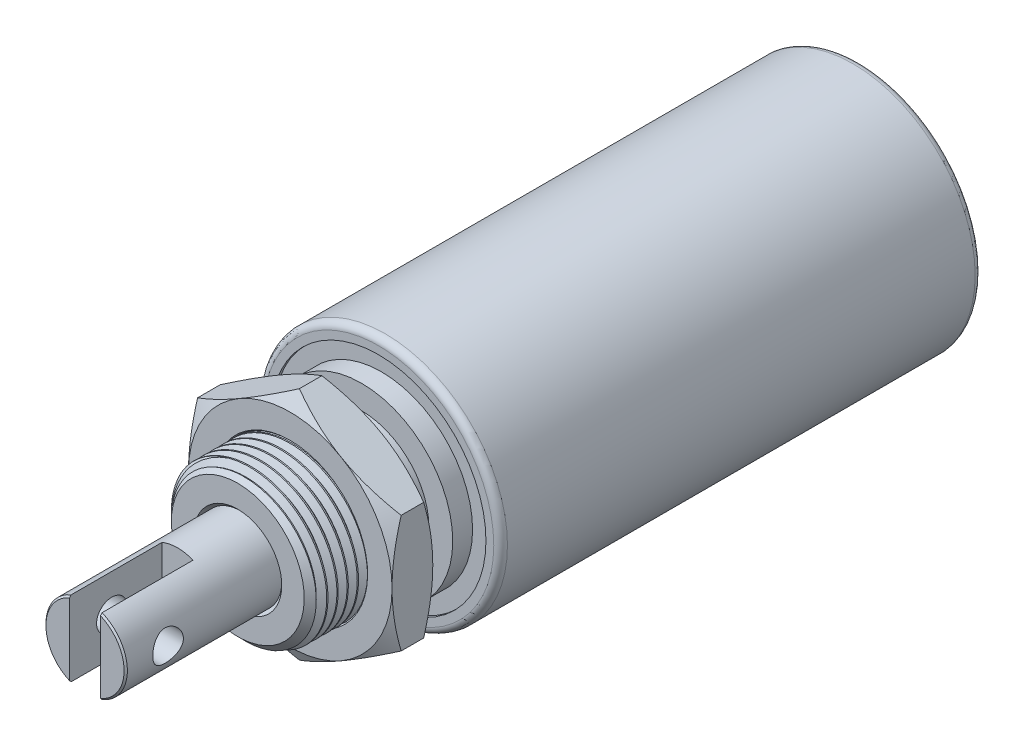
SolidWorks part; units mm, degrees
ref_plane "Front Plane" through (0, 0, 0) normal (0, 0, 1) x (1, 0, 0)
ref_plane "Top Plane" through (0, 0, 0) normal (0, 1, 0) x (1, 0, 0)
ref_plane "Right Plane" through (0, 0, 0) normal (1, 0, 0) x (0, 0, -1)
sketch "Sketch0" plane through (0, 0, 0) normal (1, 0, 0) x (0, 0, -1)
  line L0 (0, 0) -> (39.083, 0) construction
  line L1 (0, 0) -> (-21.5646, 0) construction
  line L2 (39.083, 9.525) -> (39.083, -9.525) construction
  line L3 (0, 5.9436) -> (0, -5.9436) construction
  line L4 (-21.5646, 3.175) -> (-21.5646, -3.175) construction
  line L5 (-21.5646, 0) -> (-34.2646, 0) construction
  point P10 (-18.2626, 0)
  point P12 (-9.652, 0)
  dimension "D1" = 18.2626
  dimension "Lg." = 39.083
  dimension "Dia." = 19.05
  dimension "Rod Dia." = 6.35
  dimension "A" = 21.5646
  dimension "Thread OD" = 11.8872
  dimension "Stroke" = 12.7
  dimension "D2" = 3.302
  dimension "D3" = 9.652
sketch "Sketch1" plane through (0, 0, 0) normal (1, 0, 0) x (0, 0, -1)
  line L0 (39.083, 0) -> (0, 0) construction
  line L1 (38.3286, 9.525) -> (1.8542, 9.525)
  line L2 (39.083, 2.0066) -> (39.083, 0)
  line L3 (39.083, 0) -> (0, 0)
  line L4 (1.5494, 8.382) -> (1.5494, 7.112)
  line L5 (38.862, 2.2276) -> (38.862, 8.9916)
  line L6 (1.3208, 8.9916) -> (1.3208, 8.382)
  line L7 (1.3208, 8.382) -> (1.5494, 8.382)
  line L8 (1.5494, 7.112) -> (0, 7.112)
  line L9 (0, 7.112) -> (0, 0)
  arc A0 (39.083, 2.0066) -> (38.862, 2.2276) centre (38.862, 2.0066) ccw
  arc A1 (38.862, 8.9916) -> (38.3286, 9.525) centre (38.3286, 8.9916) ccw
  arc A2 (1.3208, 8.9916) -> (1.8542, 9.525) centre (1.8542, 8.9916) cw
  dimension "D1" = 0.5334
  dimension "D4" = 1.3208
  dimension "D2" = 0.221
  dimension "D3" = 4.0132
  dimension "D5" = 16.764
  dimension "D6" = 0.2286
  dimension "D7" = 14.224
revolve "Revolve1" add sketch "Sketch1" angle 360 mid plane about L0
sketch "Sketch2" plane through (0, 0, 0) normal (1, 0, 0) x (0, 0, -1)
  line L0 (0, 0) -> (-21.5646, 0) construction
  line L3 (-9.652, 3.429) -> (-9.652, 5.1816)
  line L4 (-9.652, 5.1816) -> (-8.89, 5.9436)
  line L5 (-8.89, 5.9436) -> (-2.3114, 5.9436)
  line L6 (-2.3114, 5.9436) -> (-1.6256, 5.2578)
  line L7 (-1.6256, 5.2578) -> (0, 5.2578)
  line L8 (0, 5.2578) -> (0, 3.175)
  line L9 (-9.398, 3.175) -> (0, 3.175)
  line L11 (-9.398, 3.175) -> (-9.652, 3.429)
  dimension "D1" = 1.6256
  dimension "D2" = 45
  dimension "D3" = 45
  dimension "D4" = 0.762
  dimension "D5" = 9.652
  dimension "D6" = 0.6858
  dimension "D7" = 45
  dimension "D8" = 0.254
revolve "Revolve2" add sketch "Sketch2" angle 360 mid plane about L0
sketch "Sketch3" plane through (0, 0, 0) normal (1, 0, 0) x (0, 0, -1)
  line L0 (-21.5646, 0) -> (0, 0) construction
  line L1 (-21.4376, 3.175) -> (-21.5646, 3.048)
  line L2 (0, 0) -> (-21.5646, 0)
  line L3 (0, 0) -> (0, 3.175)
  line L4 (0, 3.175) -> (-21.4376, 3.175)
  line L5 (-21.5646, 0) -> (-21.5646, 3.048)
  line L6 (-21.4376, 3.175) -> (-21.5646, 3.175) construction
  line L7 (-21.5646, 3.175) -> (-21.5646, 3.048) construction
  dimension "D1" = 0.127
revolve "Revolve3" add sketch "Sketch3" angle 360 mid plane about L2
sketch "Sketch4" plane through (0, 0, 0) normal (0, 1, 0) x (0, 0, -1)
  line L1 (-21.5646, 1.2065) -> (-14.351, 1.2065)
  line L2 (-21.5646, 1.2065) -> (-21.5646, -1.2065)
  line L3 (-21.5646, -1.2065) -> (-14.351, -1.2065)
  line L4 (-14.351, 1.2065) -> (-14.351, -1.2065)
  dimension "D1" = 2.413
  dimension "D2" = 7.2136
extrude "Cut-Extrude1" cut sketch "Sketch4" against normal up to surface and the other way up to surface up to face at (0, 3.175, 21.4376) other way up to face at (0, 3.175, 21.4376)
sketch "Sketch5" plane through (0, 0, 0) normal (1, 0, 0) x (0, -1, 0)
  line L0 (0, -21.5646) -> (0, -18.2626) construction
  circle A0 centre (0, -18.2626) radius 1.1938
  dimension "D1" = 2.3876
extrude "Cut-Extrude2" cut sketch "Sketch5" along normal up to surface and the other way up to surface up to face at (0, 0, 17.8943) other way up to face at (0, 0, 17.8943)
sketch "Sketch6" plane through (0, 0, 9.652) normal (0, 0, 1) x (1, 0, 0)
  circle A1 centre (0, 0) radius 5.9436
  point P1 (0, 5.9436)
curve "Helix/Spiral1" pitch 0.7937 height 8.8201 radius 5.9436 centre (0, 0, 9.652) axis (0, 0, -1) start towards (0, 1, 0) parameters "Pitch"=0.7937
sketch "Sketch7" plane through (0, 0, 0) normal (1, 0, 0) x (0, 0, -1)
  line L0 (-10.3961, 6.0295) -> (-9.6024, 6.0295) construction
  line L1 (-9.6024, 6.0295) -> (-9.9993, 5.3421) construction
  line L2 (-9.9993, 5.3421) -> (-10.3961, 6.0295) construction
  line L3 (-10.0489, 5.428) -> (-9.9497, 5.428) construction
  line L4 (-10.3465, 5.9436) -> (-9.652, 5.9436) construction
  line L5 (-9.9993, 5.3421) -> (-9.9993, 5.428) construction
  line L6 (-9.9993, 5.9436) -> (-9.9993, 6.0295) construction
  line L7 (-10.0489, 5.428) -> (-9.9497, 5.428)
  line L8 (-9.9497, 5.428) -> (-9.6272, 5.9866)
  line L9 (-9.6272, 5.9866) -> (-10.3713, 5.9866)
  line L10 (-10.3713, 5.9866) -> (-10.0489, 5.428)
  line L11 (-9.9993, 5.3421) -> (-9.9993, -5.9436) construction
  line L12 (-9.9993, -5.9436) -> (-9.2055, -5.9436) construction
  line L13 (-9.2055, -5.9436) -> (-8.4118, -5.9436) construction
  line L14 (-8.4118, -5.9436) -> (-7.618, -5.9436) construction
  line L15 (-8.89, -5.9436) -> (-2.3114, -5.9436) construction
  point P15 (-9.9993, 5.9866)
  dimension "D1" = 0.7937
  dimension "D2" = 0.0992
sweep "Cut-Sweep1" cut profiles "Sketch7" path "Helix/Spiral1" align with end faces yes
move or copy body "Body-Move/Copy1" bodies to move or copy 107 copy yes number of copies 1 translate (0, 0, 12.7)
sketch "SketchX" plane through (0, 0, 0) normal (1, 0, 0) x (0, 0, -1)
  line L0 (-34.1376, -2.9368) -> (-27.051, -2.9368) construction
  line L1 (-34.2646, 2.799) -> (-34.2646, -2.799) construction
  line L2 (-34.1376, 2.9368) -> (-27.051, 2.9368) construction
  line L7 (-27.051, 3.175) -> (-27.051, 2.9368) construction
  line L8 (-12.7, 3.175) -> (-27.051, 3.175) construction
  line L11 (-27.051, -2.9368) -> (-27.051, -3.175) construction
  line L12 (-27.051, -3.175) -> (-12.7, -3.175) construction
  line L13 (-34.1376, -2.9368) -> (-27.051, -2.9368)
  line L14 (-34.2646, 2.799) -> (-34.2646, -2.799)
  line L15 (-34.1376, 2.9368) -> (-27.051, 2.9368)
  line L16 (-27.051, 3.175) -> (-27.051, 2.9368)
  line L17 (-14.351, 3.175) -> (-27.051, 3.175)
  line L18 (-27.051, -2.9368) -> (-27.051, -3.175)
  line L19 (-27.051, -3.175) -> (-14.351, -3.175)
  line L20 (-14.351, 3.175) -> (-14.351, 2.9368) construction
  arc A1 (-34.2646, -2.799) -> (-34.1376, -2.9368) centre (4.056, 32.3945) ccw construction
  circle A2 centre (-30.9626, 0) radius 1.1938 construction
  arc A3 (-34.1376, 2.9368) -> (-34.2646, 2.799) centre (4.056, -32.3945) ccw construction
  arc A4 (-34.2646, -2.799) -> (-34.1376, -2.9368) centre (4.056, 32.3945) ccw
  circle A5 centre (-30.9626, 0) radius 1.1938
  arc A6 (-34.1376, 2.9368) -> (-34.2646, 2.799) centre (4.056, -32.3945) ccw
delete or keep bodies "Body-Delete1" type delete bodies bodies 108
sketch "Sketch8" plane through (0, 0, -38.862) normal (0, 0, -1) x (-1, 0, 0)
  line L0 (-6.604, -2.54) -> (-6.604, 2.54) construction
  line L1 (0, 0) -> (-6.604, 0) construction
  circle A0 centre (-6.604, 2.54) radius 0.254
  circle A1 centre (-6.604, -2.54) radius 0.254
  dimension "D1" = 0.508
  dimension "D2" = 5.08
  dimension "D3" = 6.604
extrude "Boss-Extrude1" [suppressed] add sketch "Sketch8" along normal blind 165.1
sketch "Sketch9" plane through (0, 0, -38.862) normal (0, 0, -1) x (-1, 0, 0)
  circle A0 centre (-6.604, 2.54) radius 0.4826
  circle A1 centre (-6.604, -2.54) radius 0.4826
  circle A3 centre (-6.604, -2.54) radius 0.254
  circle A4 centre (-6.604, -2.54) radius 0.254
  circle A5 centre (-6.604, 2.54) radius 0.254
  circle A6 centre (-6.604, 2.54) radius 0.254
  dimension "D3" = 0.9652
  dimension "D1" = 0
  dimension "D2" = 0
extrude "Boss-Extrude2" [suppressed] add sketch "Sketch9" along normal blind 152.4
sketch "Sketch10" plane through (0, 0, 0) normal (0, 0, 1) x (1, 0, 0)
  line L0 (0, 5.9436) -> (0, 7.9375) construction
  line L1 (0, 9.1654) -> (-7.9375, 4.5827)
  line L2 (-7.9375, 4.5827) -> (-7.9375, -4.5827)
  line L3 (-7.9375, -4.5827) -> (0, -9.1654)
  line L4 (0, -9.1654) -> (7.9375, -4.5827)
  line L5 (7.9375, -4.5827) -> (7.9375, 4.5827)
  line L6 (7.9375, 4.5827) -> (0, 9.1654)
  circle A0 centre (0, 0) radius 5.9436
  circle A1 centre (0, 0) radius 7.9375 construction
  dimension "D1" = 15.875
extrude "Boss-Extrude3" add sketch "Sketch10" along normal blind 3.175 from offset 2.3813 separate body
sketch "Sketch11" plane through (0, 0, 0) normal (1, 0, 0) x (0, 0, -1)
  line L0 (-2.3813, 0) -> (-5.5563, 0) construction
  line L1 (-5.5563, 5.9436) -> (-5.5563, -5.9436) construction
  line L2 (-2.3813, -5.9436) -> (-2.3813, 5.9436) construction
  line L3 (-5.5563, 9.1654) -> (-5.5563, 7.9375)
  line L4 (-5.5563, 4.5827) -> (-5.5563, 9.1654) construction
  line L5 (-5.5563, 7.9375) -> (-4.8473, 9.1654)
  line L6 (-5.5563, 9.1654) -> (-2.3813, 9.1654) construction
  line L7 (-4.8473, 9.1654) -> (-5.5563, 9.1654)
  line L8 (-2.3813, 9.1654) -> (-2.3813, 7.9375)
  line L9 (-2.3813, 4.5827) -> (-2.3813, 9.1654) construction
  line L10 (-2.3813, 7.9375) -> (-3.0902, 9.1654)
  line L11 (-3.0902, 9.1654) -> (-2.3813, 9.1654)
  line L12 (0, 7.9375) -> (-5.5563, 7.9375) construction
  line L13 (-5.5563, 6.0295) -> (-5.5563, 5.9436)
  line L14 (-5.5563, 5.9436) -> (-5.4703, 5.9436)
  line L15 (-5.4703, 5.9436) -> (-5.5563, 6.0295)
  line L16 (-2.3813, 6.0295) -> (-2.3813, 5.9436)
  line L17 (-2.3813, 5.9436) -> (-2.4672, 5.9436)
  line L18 (-2.4672, 5.9436) -> (-2.3813, 6.0295)
  line L19 (-9.9993, 6.0295) -> (-5.5563, 6.0295) construction
  dimension "D1" = 30
revolve "Cut-Revolve1" cut sketch "Sketch11" angle 360 about L0
equation "\"D3@Helix/Spiral1\" = \"Pitch@Helix/Spiral1\" + \"D5@Sketch2\" - \"D1@Sketch2\""
equation "\"D1@Sketch7\" = \"Pitch@Helix/Spiral1\""
equation "\"D2@Sketch7\" = \"D1@Sketch7\" / 8"
